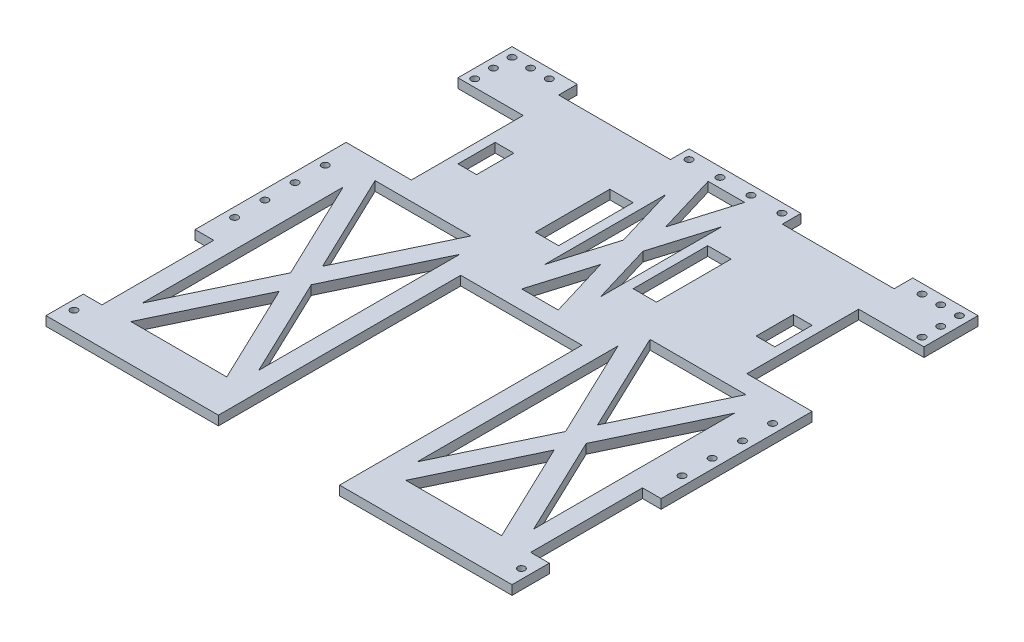
SolidWorks part; units mm, degrees
material "7050-T73510"
ref_plane "Front Plane" through (0, 0, 0) normal (0, 0, 1) x (1, 0, 0)
ref_plane "Top Plane" through (0, 0, 0) normal (0, 1, 0) x (1, 0, 0)
ref_plane "Right Plane" through (0, 0, 0) normal (1, 0, 0) x (0, 0, -1)
sketch "Sketch1" plane through (0, 0, 0) normal (0, 1, 0) x (1, 0, 0)
  line L0 (0, -55) -> (0, 55) construction
  line L1 (-158.75, -76.2) -> (158.75, -76.2)
  line L2 (-158.75, -76.2) -> (-158.75, 76.2)
  line L3 (-158.75, 76.2) -> (158.75, 76.2)
  line L4 (158.75, -76.2) -> (158.75, 76.2)
  line L5 (-158.75, -76.2) -> (158.75, 76.2) construction
  line L6 (-158.75, 76.2) -> (158.75, -76.2) construction
  line L7 (-158.75, -76.2) -> (-25.4, -76.2)
  line L8 (-158.75, -76.2) -> (-158.75, -241.3)
  line L9 (-158.75, -241.3) -> (-25.4, -241.3)
  line L10 (-25.4, -76.2) -> (-25.4, -241.3)
  line L11 (25.4, -76.2) -> (25.4, -241.3)
  line L12 (158.75, -241.3) -> (25.4, -241.3)
  line L13 (158.75, -76.2) -> (158.75, -241.3)
  line L14 (158.75, -76.2) -> (25.4, -76.2)
  line L15 (-41.275, -76.2) -> (-41.275, -241.3)
  line L16 (41.275, -76.2) -> (41.275, -241.3)
  point P0 (0, 0)
  dimension "D1" = 317.5
  dimension "D2" = 152.4
  dimension "D3" = 317.5
  dimension "D4" = 50.8
  dimension "D5" = 15.875
extrude "Boss-Extrude1" add sketch "Sketch1" along normal blind 6.35 contours L15 L1 L8 L9 | L14 L16 L12 L13 | L1 L7 L14 L4 L3 L2 region at (0, 0, 0) region at (-100.0125, 0, 158.75) region at (100.0125, 0, 158.75)
sketch "Sketch2" plane through (0, 6.35, 0) normal (0, 1, 0) x (1, 0, 0)
  line L0 (158.75, -241.3) -> (158.75, 76.2) construction
  line L1 (158.75, 39.37) -> (114.3, 39.37)
  line L2 (158.75, 39.37) -> (158.75, -36.83)
  line L3 (158.75, -36.83) -> (114.3, -36.83)
  line L4 (114.3, 39.37) -> (114.3, -36.83)
  line L5 (-158.75, 76.2) -> (158.75, 76.2) construction
  line L6 (158.75, -139.7) -> (146.05, -139.7)
  line L7 (158.75, -139.7) -> (158.75, -215.9)
  line L8 (158.75, -215.9) -> (146.05, -215.9)
  line L9 (146.05, -139.7) -> (146.05, -215.9)
  line L10 (0, -3.4925) -> (0, 3.4925) construction
  line L11 (-158.75, -215.9) -> (-146.05, -215.9)
  line L12 (-146.05, -139.7) -> (-146.05, -215.9)
  line L13 (-158.75, -139.7) -> (-146.05, -139.7)
  line L14 (-158.75, -139.7) -> (-158.75, -215.9)
  line L15 (-158.75, -36.83) -> (-114.3, -36.83)
  line L16 (-114.3, 39.37) -> (-114.3, -36.83)
  line L17 (-158.75, 39.37) -> (-114.3, 39.37)
  line L18 (-158.75, 39.37) -> (-158.75, -36.83)
  line L19 (-114.3, 63.5) -> (-38.1, 63.5)
  line L20 (114.3, 76.2) -> (38.1, 76.2)
  line L21 (114.3, 76.2) -> (114.3, 63.5)
  line L22 (114.3, 63.5) -> (38.1, 63.5)
  line L23 (38.1, 76.2) -> (38.1, 63.5)
  line L24 (-38.1, 76.2) -> (-38.1, 63.5)
  line L25 (-114.3, 76.2) -> (-38.1, 76.2)
  line L26 (-114.3, 76.2) -> (-114.3, 63.5)
  dimension "D1" = 44.45
  dimension "D2" = 12.7
  dimension "D3" = 76.2
  dimension "D4" = 76.2
  dimension "D5" = 36.83
  dimension "D6" = 215.9
  dimension "D7" = 76.2
  dimension "D8" = 12.7
  dimension "D9" = 76.2
extrude "Cut-Extrude1" cut sketch "Sketch2" against normal through all
sketch "Sketch4" plane through (0, 6.35, 0) normal (0, 1, 0) x (1, 0, 0)
  line L0 (41.275, -76.2) -> (41.275, -241.3) construction
  line L1 (53.975, -215.9) -> (133.35, -215.9)
  line L2 (53.975, -215.9) -> (53.975, -49.53)
  line L3 (53.975, -49.53) -> (133.35, -49.53)
  line L4 (133.35, -215.9) -> (133.35, -49.53)
  line L5 (146.05, -139.7) -> (146.05, -215.9) construction
  line L6 (158.75, -241.3) -> (41.275, -241.3) construction
  line L7 (53.975, -215.9) -> (133.35, -49.53) construction
  line L8 (53.975, -49.53) -> (133.35, -215.9) construction
  line L9 (133.35, -201.1532) -> (61.0107, -49.53)
  line L10 (126.3143, -215.9) -> (53.975, -64.2768)
  line L11 (53.975, -201.1532) -> (126.3143, -49.53)
  line L12 (61.0107, -215.9) -> (133.35, -64.2768)
  line L13 (114.3, -36.83) -> (158.75, -36.83) construction
  line L14 (0, -3.4925) -> (0, 3.4925) construction
  line L15 (-53.975, -201.1532) -> (-126.3143, -49.53)
  line L16 (-126.3143, -215.9) -> (-53.975, -64.2768)
  line L17 (-133.35, -201.1532) -> (-61.0107, -49.53)
  line L18 (-61.0107, -215.9) -> (-133.35, -64.2768)
  line L19 (-53.975, -49.53) -> (-133.35, -49.53)
  line L20 (-133.35, -215.9) -> (-133.35, -49.53)
  line L21 (-53.975, -215.9) -> (-133.35, -215.9)
  line L22 (-53.975, -215.9) -> (-53.975, -49.53)
  point P18 (116.9135, -166.7022)
  dimension "D1" = 12.7
  dimension "D2" = 12.7
  dimension "D3" = 25.4
  dimension "D4" = 12.7
  dimension "D5" = 12.7
extrude "Cut-Extrude3" cut sketch "Sketch4" against normal through all contours L12 L9 L4 | L12 L1 L10 | L2 L11 L10 | L9 L11 L3 | L21 L18 L16 | L20 L17 L18 | L17 L19 L15 | L15 L22 L16 region at (93.6625, 6.35, 193.0873) region at (64.8589, 6.35, 132.715) region at (122.4661, 6.35, 132.715) region at (93.6625, 6.35, 72.3427) region at (-64.8589, 6.35, 132.715) region at (-93.6625, 6.35, 72.3427) region at (-93.6625, 6.35, 193.0873) region at (-122.4661, 6.35, 132.715)
sketch "Sketch3" plane through (0, 6.35, 0) normal (0, 1, 0) x (1, 0, 0)
  line L0 (-41.275, -76.2) -> (41.275, -76.2) construction
  line L1 (-41.275, -25.4) -> (-25.4, -25.4)
  line L2 (-41.275, -25.4) -> (-41.275, 25.4)
  line L3 (-41.275, 25.4) -> (-25.4, 25.4)
  line L4 (-25.4, -25.4) -> (-25.4, 25.4)
  line L5 (0, -3.4925) -> (0, 3.4925) construction
  line L6 (41.275, 25.4) -> (25.4, 25.4)
  line L7 (25.4, -25.4) -> (25.4, 25.4)
  line L8 (41.275, -25.4) -> (25.4, -25.4)
  line L9 (41.275, -25.4) -> (41.275, 25.4)
  line L10 (114.3, 39.37) -> (114.3, -36.83) construction
  line L11 (95.25, 13.97) -> (107.95, 13.97)
  line L12 (95.25, 13.97) -> (95.25, -11.43)
  line L13 (95.25, -11.43) -> (107.95, -11.43)
  line L14 (107.95, 13.97) -> (107.95, -11.43)
  line L15 (38.1, 63.5) -> (114.3, 63.5) construction
  line L16 (-95.25, -11.43) -> (-107.95, -11.43)
  line L17 (-107.95, 13.97) -> (-107.95, -11.43)
  line L18 (-95.25, 13.97) -> (-107.95, 13.97)
  line L19 (-95.25, 13.97) -> (-95.25, -11.43)
  dimension "D1" = 50.8
  dimension "D2" = 15.875
  dimension "D3" = 50.8
  dimension "D4" = 50.8
  dimension "D5" = 25.4
  dimension "D6" = 12.7
  dimension "D7" = 6.35
  dimension "D8" = 49.53
extrude "Cut-Extrude2" cut sketch "Sketch3" against normal through all
sketch "Sketch6" plane through (0, 6.35, 0) normal (0, 1, 0) x (1, 0, 0)
  line L0 (-25.4, -25.4) -> (-25.4, 25.4) construction
  line L1 (-19.05, 63.5) -> (19.05, 63.5)
  line L2 (-19.05, 63.5) -> (-19.05, -63.5)
  line L3 (-19.05, -63.5) -> (19.05, -63.5)
  line L4 (19.05, 63.5) -> (19.05, -63.5)
  line L5 (25.4, 25.4) -> (25.4, -25.4) construction
  line L6 (-38.1, 76.2) -> (38.1, 76.2) construction
  line L7 (-41.275, -76.2) -> (41.275, -76.2) construction
  line L8 (-19.05, -63.5) -> (19.05, 63.5) construction
  line L9 (19.05, -63.5) -> (-19.05, 63.5) construction
  line L10 (12.4204, -63.5) -> (-19.05, 41.4014)
  line L11 (-12.4204, 63.5) -> (19.05, -41.4014)
  line L12 (-19.05, -41.4014) -> (12.4204, 63.5)
  line L13 (19.05, 41.4014) -> (-12.4204, -63.5)
  dimension "D1" = 6.35
  dimension "D2" = 6.35
  dimension "D3" = 12.7
  dimension "D4" = 12.7
  dimension "D5" = 12.7
  dimension "D6" = 12.7
extrude "Cut-Extrude5" cut sketch "Sketch6" against normal through all contours L10 L13 L3 | L4 L13 L11 | L2 L12 L10 | L11 L12 L1 region at (0, 6.35, -49.6995) region at (-14.9099, 6.35, 0) region at (14.9099, 6.35, 0) region at (0, 6.35, 49.6995)
sketch "Sketch7" plane through (0, 6.35, 0) normal (0, 1, 0) x (1, 0, 0)
  line L0 (158.75, -139.7) -> (146.05, -139.7) construction
  line L1 (158.75, -139.7) -> (158.75, -36.83) construction
  line L2 (0, -3.4925) -> (0, 3.4925) construction
  line L3 (158.75, -241.3) -> (41.275, -241.3) construction
  line L4 (-38.1, 76.2) -> (-38.1, 63.5) construction
  line L5 (114.3, 76.2) -> (158.75, 76.2) construction
  line L6 (-38.1, 76.2) -> (38.1, 76.2) construction
  circle A0 centre (152.4, -119.126) radius 2.413
  circle A1 centre (152.4, -98.552) radius 2.413
  circle A2 centre (152.4, -77.978) radius 2.413
  circle A3 centre (152.4, -57.404) radius 2.413
  circle A4 centre (-152.4, -57.404) radius 2.413
  circle A5 centre (-152.4, -77.978) radius 2.413
  circle A6 centre (-152.4, -98.552) radius 2.413
  circle A7 centre (-152.4, -119.126) radius 2.413
  circle A8 centre (152.4, -228.6) radius 2.413
  circle A9 centre (152.4, 69.85) radius 2.413
  circle A10 centre (139.7, 69.85) radius 2.413
  circle A11 centre (127, 69.85) radius 2.413
  circle A12 centre (152.4, 57.15) radius 2.413
  circle A13 centre (152.4, 44.45) radius 2.413
  circle A14 centre (-152.4, 44.45) radius 2.413
  circle A15 centre (-152.4, 57.15) radius 2.413
  circle A16 centre (-127, 69.85) radius 2.413
  circle A17 centre (-139.7, 69.85) radius 2.413
  circle A18 centre (-152.4, 69.85) radius 2.413
  circle A19 centre (-152.4, -228.6) radius 2.413
  circle A20 centre (-31.75, 69.85) radius 2.413
  circle A21 centre (-10.668, 69.85) radius 2.413
  circle A22 centre (10.414, 69.85) radius 2.413
  circle A23 centre (31.496, 69.85) radius 2.413
  dimension "D1" = 4.826
  dimension "D3" = 6.35
  dimension "D5" = 12.7
  dimension "D6" = 6.35
  dimension "D9" = 4.826
  dimension "D2" = 20.574
  dimension "D8" = 3
  dimension "D10" = 6.35
  dimension "D11" = 6.35
  dimension "D4" = 4
  dimension "D7" = 3
  dimension "D12" = 4
extrude "Cut-Extrude6" cut sketch "Sketch7" against normal through all
sketch "Sketch5" plane through (0, 6.35, 0) normal (0, 1, 0) x (1, 0, 0)
  line L0 (0, -3.4925) -> (0, 3.4925) construction
  line L2 (-38.1, 76.2) -> (38.1, 76.2) construction
  line L3 (41.275, -25.4) -> (41.275, 25.4) construction
  line L4 (114.3, 63.5) -> (38.1, 63.5) construction
  circle A0 centre (12.7, 63.5) radius 6.35
  circle A1 centre (12.7, 50.8) radius 6.35
  circle A2 centre (12.7, 38.1) radius 6.35
  circle A3 centre (12.7, 25.4) radius 6.35
  circle A4 centre (12.7, 12.7) radius 6.35
  circle A11 centre (0, 50.8) radius 6.35
  circle A12 centre (0, 38.1) radius 6.35
  circle A13 centre (0, 25.4) radius 6.35
  circle A14 centre (0, 12.7) radius 6.35
  circle A21 centre (-12.7, 50.8) radius 6.35
  circle A22 centre (-12.7, 38.1) radius 6.35
  circle A23 centre (-12.7, 25.4) radius 6.35
  circle A24 centre (-12.7, 12.7) radius 6.35
  circle A31 centre (0, 63.5) radius 6.35
  circle A32 centre (-12.7, 63.5) radius 6.35
  circle A33 centre (53.975, 50.8) radius 3.175
  circle A34 centre (66.675, 50.8) radius 3.175
  circle A35 centre (79.375, 50.8) radius 3.175
  circle A36 centre (66.675, 38.1) radius 3.175
  circle A37 centre (79.375, 38.1) radius 3.175
  circle A38 centre (66.675, 25.4) radius 3.175
  circle A39 centre (79.375, 25.4) radius 3.175
  circle A40 centre (66.675, 12.7) radius 3.175
  circle A41 centre (79.375, 12.7) radius 3.175
  circle A42 centre (66.675, 0) radius 3.175
  circle A43 centre (79.375, 0) radius 3.175
  circle A44 centre (66.675, -12.7) radius 3.175
  circle A45 centre (79.375, -12.7) radius 3.175
  circle A46 centre (66.675, -25.4) radius 3.175
  circle A47 centre (79.375, -25.4) radius 3.175
  circle A48 centre (66.675, -38.1) radius 3.175
  circle A49 centre (79.375, -38.1) radius 3.175
  circle A50 centre (53.975, 38.1) radius 3.175
  circle A51 centre (53.975, 25.4) radius 3.175
  circle A52 centre (53.975, 12.7) radius 3.175
  circle A53 centre (53.975, 0) radius 3.175
  circle A54 centre (53.975, -12.7) radius 3.175
  circle A55 centre (53.975, -25.4) radius 3.175
  circle A56 centre (53.975, -38.1) radius 3.175
  circle A57 centre (-53.975, -38.1) radius 3.175
  circle A58 centre (-53.975, -25.4) radius 3.175
  circle A59 centre (-53.975, -12.7) radius 3.175
  circle A60 centre (-53.975, 0) radius 3.175
  circle A61 centre (-53.975, 12.7) radius 3.175
  circle A62 centre (-53.975, 25.4) radius 3.175
  circle A63 centre (-53.975, 38.1) radius 3.175
  circle A64 centre (-79.375, -38.1) radius 3.175
  circle A65 centre (-66.675, -38.1) radius 3.175
  circle A66 centre (-79.375, -25.4) radius 3.175
  circle A67 centre (-66.675, -25.4) radius 3.175
  circle A68 centre (-79.375, -12.7) radius 3.175
  circle A69 centre (-66.675, -12.7) radius 3.175
  circle A70 centre (-79.375, 0) radius 3.175
  circle A71 centre (-66.675, 0) radius 3.175
  circle A72 centre (-79.375, 12.7) radius 3.175
  circle A73 centre (-66.675, 12.7) radius 3.175
  circle A74 centre (-79.375, 25.4) radius 3.175
  circle A75 centre (-66.675, 25.4) radius 3.175
  circle A76 centre (-79.375, 38.1) radius 3.175
  circle A77 centre (-66.675, 38.1) radius 3.175
  circle A78 centre (-79.375, 50.8) radius 3.175
  circle A79 centre (-66.675, 50.8) radius 3.175
  circle A80 centre (-53.975, 50.8) radius 3.175
  dimension "D1" = 12.7
  dimension "D6" = 6.35
  dimension "D2" = 12.7
  dimension "D3" = 12.7
  dimension "D7" = 12.7
  dimension "D8" = 12.7
  dimension "D4" = 5
  dimension "D5" = 3
  dimension "D9" = 3
  dimension "D10" = 8
